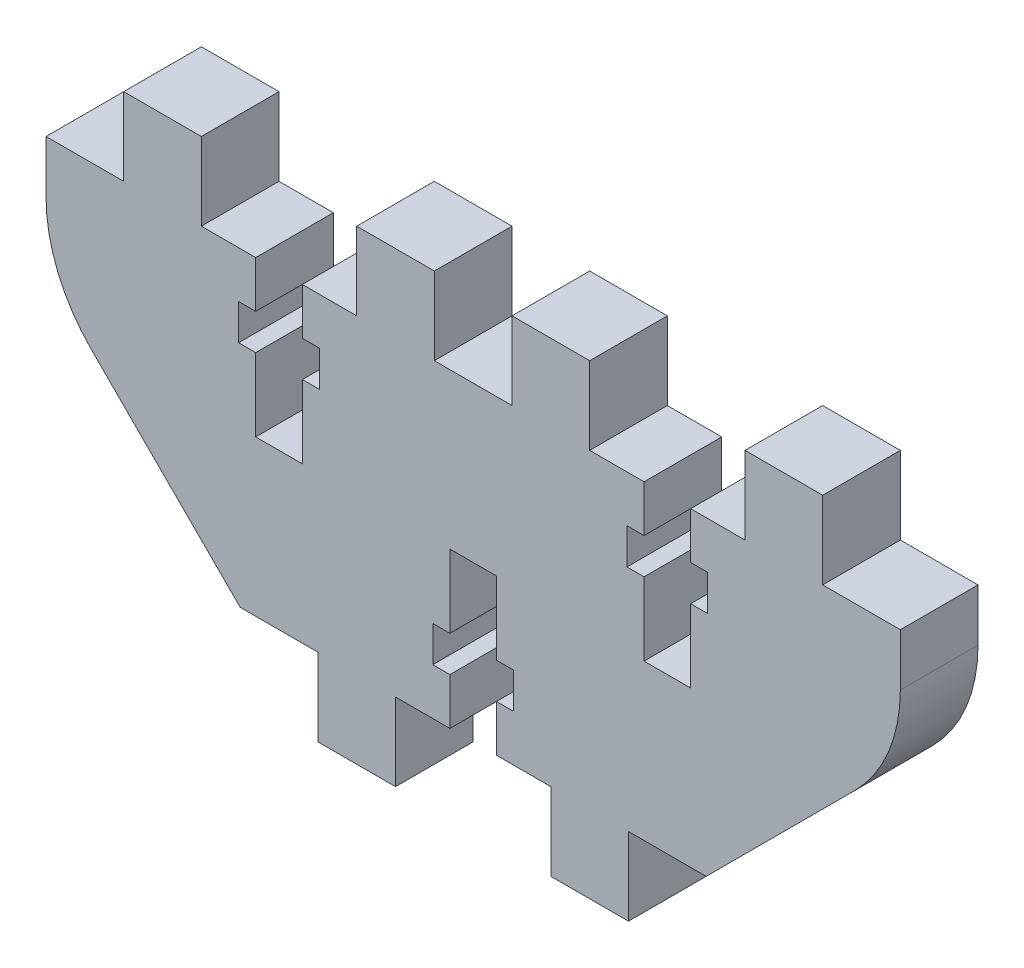
SolidWorks part; units mm, degrees
ref_plane "Plan de face" through (0, 0, 0) normal (0, 0, 1) x (1, 0, 0)
ref_plane "Plan de dessus" through (0, 0, 0) normal (0, 1, 0) x (1, 0, 0)
ref_plane "Plan de droite" through (0, 0, 0) normal (1, 0, 0) x (0, 0, -1)
sketch "Esquisse1" plane through (0, 0, 0) normal (0, 0, 1) x (1, 0, 0)
  line L0 (15, 0) -> (27.5, 12.5)
  line L1 (0, 0) -> (0, -30.9586) construction
  line L2 (-10, 0) -> (-15, 0)
  line L3 (-27.5, 12.5) -> (-27.5, 20)
  line L4 (-15, 0) -> (-27.5, 12.5)
  line L5 (-2.5, 20) -> (2.5, 20)
  line L6 (10, 0) -> (15, 0)
  line L8 (27.5, 12.5) -> (27.5, 20)
  line L9 (27.5, 20) -> (22.5, 20)
  line L10 (-22.5, 20) -> (-27.5, 20)
  line B0 (-2.6, 3) -> (-2.6, 5.3)
  line B1 (1.5, 5.3) -> (1.5, 10)
  line B2 (-1.5, 10) -> (-1.5, 5.3)
  line B3 (-2.6, 5.3) -> (-1.5, 5.3)
  line B4 (0, 0) -> (0, 11.2208) construction
  line B5 (-1.5, 0) -> (-5, 0)
  line B6 (-5, -5) -> (-10, -5)
  line B7 (-10, -5) -> (-10, 0)
  line B8 (-5, -5) -> (-5, 0)
  line B9 (1.5, 0) -> (5, 0)
  line B10 (5, 0) -> (5, -5)
  line B11 (5, -5) -> (10, -5)
  line B12 (10, -5) -> (10, 0)
  line B13 (-1.5, 0) -> (1.5, 0) construction
  line B14 (1.5, 0) -> (1.5, 3)
  line B15 (1.5, 5.3) -> (2.6, 5.3)
  line B16 (2.6, 3) -> (1.5, 3)
  line B17 (1.5, 10) -> (-1.5, 10)
  line B18 (-1.5, 3) -> (-2.6, 3)
  line B19 (2.6, 5.3) -> (2.6, 3)
  line B20 (-1.5, 3) -> (-1.5, 0)
  line B21 (0, 10) -> (0, 0) construction
  line B22 (15.1, 17) -> (15.1, 14.7)
  line B23 (11, 14.7) -> (11, 10)
  line B24 (14, 10) -> (14, 14.7)
  line B25 (15.1, 14.7) -> (14, 14.7)
  line B26 (12.5, 20) -> (12.5, 8.7792) construction
  line B27 (14, 20) -> (17.5, 20)
  line B28 (17.5, 25) -> (22.5, 25)
  line B29 (22.5, 25) -> (22.5, 20)
  line B30 (17.5, 25) -> (17.5, 20)
  line B31 (11, 20) -> (7.5, 20)
  line B32 (7.5, 20) -> (7.5, 25)
  line B33 (7.5, 25) -> (2.5, 25)
  line B34 (2.5, 25) -> (2.5, 20)
  line B35 (14, 20) -> (11, 20) construction
  line B36 (11, 20) -> (11, 17)
  line B37 (11, 14.7) -> (9.9, 14.7)
  line B38 (9.9, 17) -> (11, 17)
  line B39 (11, 10) -> (14, 10)
  line B40 (14, 17) -> (15.1, 17)
  line B41 (9.9, 14.7) -> (9.9, 17)
  line B42 (14, 17) -> (14, 20)
  line B43 (12.5, 10) -> (12.5, 20) construction
  line B44 (-15.1, 17) -> (-15.1, 14.7)
  line B45 (-11, 14.7) -> (-11, 10)
  line B46 (-14, 10) -> (-14, 14.7)
  line B47 (-15.1, 14.7) -> (-14, 14.7)
  line B48 (-12.5, 20) -> (-12.5, 8.7792) construction
  line B49 (-14, 20) -> (-17.5, 20)
  line B50 (-17.5, 25) -> (-22.5, 25)
  line B51 (-22.5, 25) -> (-22.5, 20)
  line B52 (-17.5, 25) -> (-17.5, 20)
  line B53 (-11, 20) -> (-7.5, 20)
  line B54 (-7.5, 20) -> (-7.5, 25)
  line B55 (-7.5, 25) -> (-2.5, 25)
  line B56 (-2.5, 25) -> (-2.5, 20)
  line B57 (-14, 20) -> (-11, 20) construction
  line B58 (-11, 20) -> (-11, 17)
  line B59 (-11, 14.7) -> (-9.9, 14.7)
  line B60 (-9.9, 17) -> (-11, 17)
  line B61 (-11, 10) -> (-14, 10)
  line B62 (-14, 17) -> (-15.1, 17)
  line B63 (-9.9, 14.7) -> (-9.9, 17)
  line B64 (-14, 17) -> (-14, 20)
  line B65 (-12.5, 10) -> (-12.5, 20) construction
  dimension "D1" = 5
  dimension "D2" = 0
  dimension "D3" = 5
  dimension "D4" = 20
sketch_block_instance "Insert M3 plots ep 5mm-1"
sketch_block "Insert M3 plots ep 5mm" parameters "D1"=10, "D2"=5, "D3"=5
sketch_block_instance "Decoupe Insert M3-4"
sketch_block "Decoupe Insert M3" parameters "D1"=5.2, "D2"=3, "D3"=2.3, "D4"=3, "D5"=10
sketch_block_instance "Insert M3 plots ep 5mm-3"
sketch_block_instance "Insert M3 plots ep 5mm-4"
extrude "Boss.-Extru.1" add sketch "Esquisse1" along normal blind 5 contours B42 B40 B22 B25 B24 B39 B23 B37 B41 B38 B36 B31 B32 B33 B34 L4 L2 B7 B6 B8 B5 B20 B18 B0 B3 B2 B17 B1 B15 B19 B16 B14 B9 B10 B11 B12 L6 L0 L8 L9 B29 B28 B30 B27 region at (0, 11.3725, 0)
fillet "Congé1" radius 10 2 edges at (-27.5, 12.5, 2.5) (27.5, 12.5, 2.5)
